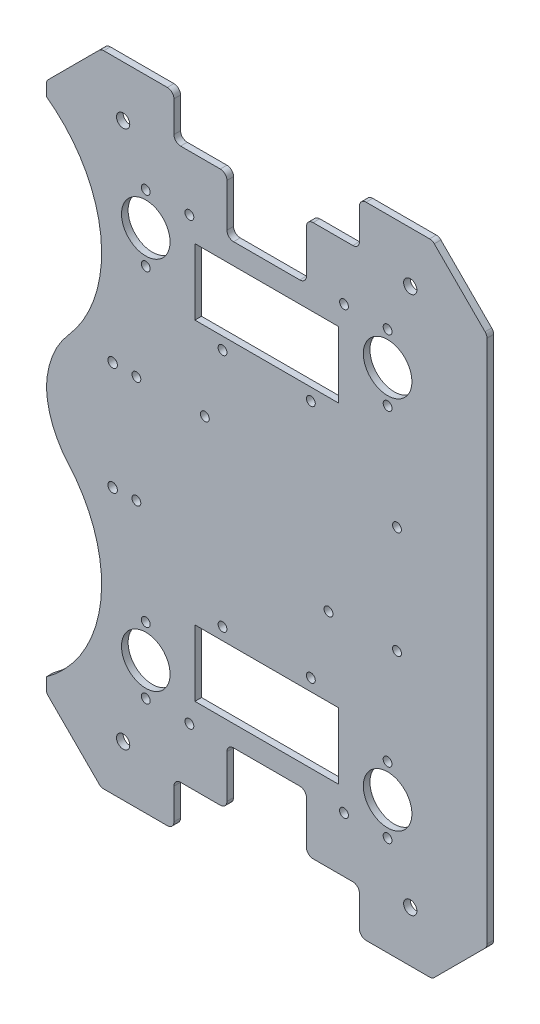
SolidWorks part; units mm, degrees
material "Alliage 1060"
ref_plane "Plan de dessus" through (0, 0, 0) normal (0, 0, 1) x (1, 0, 0)
ref_plane "Plan de droite" through (0, 0, 0) normal (0, 1, 0) x (1, 0, 0)
ref_plane "Plan de face" through (0, 0, 0) normal (1, 0, 0) x (0, 0, -1)
sketch "Esquisse1" plane through (0, 0, 0) normal (0, 0, 1) x (1, 0, 0)
  line L0 (0, 0) -> (-150, 0)
  line L1 (-150, 0) -> (-174.7487, 24.7487)
  line L2 (-174.7487, 24.7487) -> (-174.7487, 264.7487)
  line L3 (-174.7487, 264.7487) -> (-150, 289.4975)
  line L4 (-150, 289.4975) -> (0, 289.4975)
  line L5 (0, 289.4975) -> (24.7487, 264.7487)
  line L6 (24.7487, 264.7487) -> (24.7487, 24.7487)
  line L7 (24.7487, 24.7487) -> (0, 0)
  dimension "D1" = 240
  dimension "D2" = 35
  dimension "D3" = 135
  dimension "D4" = 150
extrude "Base" add sketch "Esquisse1" along normal blind 3
sketch "Esquisse3" plane through (0, 0, 0) normal (0, 0, -1) x (-1, 0, 0)
  line L0 (117, 0) -> (117, 20)
  line L1 (150, 0) -> (0, 0) construction
  line L2 (117, 20) -> (93, 20)
  line L3 (93, 20) -> (93, 45.5)
  line L4 (93, 45.5) -> (57, 45.5)
  line L5 (57, 45.5) -> (57, 20)
  line L6 (57, 20) -> (33, 20)
  line L7 (33, 20) -> (33, 0)
  line L8 (-24.7487, 144.7487) -> (174.7487, 144.7487) construction
  line L9 (-24.7487, 24.7487) -> (-24.7487, 264.7487) construction
  line L10 (174.7487, 264.7487) -> (174.7487, 24.7487) construction
  line L11 (33, 0) -> (117, 0)
  line L12 (33, 289.4975) -> (117, 289.4975)
  line L13 (117, 289.4975) -> (117, 269.4975)
  line L14 (117, 269.4975) -> (93, 269.4975)
  line L15 (93, 269.4975) -> (93, 243.9975)
  line L16 (93, 243.9975) -> (57, 243.9975)
  line L17 (57, 243.9975) -> (57, 269.4975)
  line L18 (57, 269.4975) -> (33, 269.4975)
  line L19 (33, 269.4975) -> (33, 289.4975)
  line L20 (75, 45.5) -> (75, -49954.5) construction
  line L21 (0, 289.4975) -> (150, 289.4975) construction
  line L22 (42.5, 234.4975) -> (107.5, 234.4975)
  line L23 (42.5, 234.4975) -> (42.5, 204.4975)
  line L24 (42.5, 204.4975) -> (107.5, 204.4975)
  line L25 (107.5, 234.4975) -> (107.5, 204.4975)
  line L26 (107.5, 55) -> (107.5, 85)
  line L27 (42.5, 85) -> (107.5, 85)
  line L28 (42.5, 55) -> (107.5, 55)
  line L29 (42.5, 55) -> (42.5, 85)
  circle A0 centre (40, 45) radius 2
  circle A1 centre (110, 45) radius 2
  circle A2 centre (110, 244.4975) radius 2
  circle A3 centre (40, 244.4975) radius 2
  point P4 (75, 45.5)
  point P11 (75, 0)
  point P40 (75, 234.4975)
  dimension "D7" = 4
  dimension "D5" = 25
  dimension "D1" = 20
  dimension "D2" = 24
  dimension "D3" = 36
  dimension "D4" = 25.5
  dimension "D6" = 7
  dimension "D8" = 55
  dimension "D9" = 30
  dimension "D10" = 65
extrude "Enlèv. mat.-Extru.1" cut sketch "Esquisse3" against normal through all
fillet "Congé1" radius 3 24 edges at (-174.7487, 24.7487, 1.5) (24.7487, 24.7487, 1.5) (0, 0, 1.5) (-117, 20, 1.5) (-93, 45.5, 1.5) (-93, 20, 1.5) (-150, 0, 1.5) (-117, 0, 1.5) (-57, 45.5, 1.5) (-33, 20, 1.5) (-57, 20, 1.5) (-33, 0, 1.5) (24.7487, 264.7487, 1.5) (-117, 269.4975, 1.5) (-93, 243.9975, 1.5) (-174.7487, 264.7487, 1.5) (-150, 289.4975, 1.5) (-117, 289.4975, 1.5) (-93, 269.4975, 1.5) (-57, 243.9975, 1.5) (-33, 269.4975, 1.5) (-57, 269.4975, 1.5) (-33, 289.4975, 1.5) (0, 289.4975, 1.5)
sketch "Esquisse6" plane through (0, 0, 3) normal (0, 0, 1) x (1, 0, 0)
  line L0 (-129.7487, 60) -> (-129.7487, 75) construction
  line L1 (-129.7487, 60) -> (-129.7487, 45) construction
  line L2 (-75, 231.5685) -> (-75, -49768.4315) construction
  line L4 (-42.5, 204.4975) -> (-107.5, 204.4975) construction
  line L5 (-203.2843, 144.7487) -> (49796.7157, 144.7487) construction
  line L6 (-174.7487, 263.5061) -> (-174.7487, 25.9914) construction
  line L15 (-148.7574, 0) -> (-120, 0) construction
  circle A25 centre (-129.7487, 45) radius 2
  circle A26 centre (-129.7487, 75) radius 2
  circle A27 centre (-129.7487, 60) radius 11
  circle A31 centre (-20.2513, 45) radius 2
  circle A32 centre (-20.2513, 75) radius 2
  circle A33 centre (-20.2513, 60) radius 11
  circle A34 centre (-20.2513, 229.4975) radius 11
  circle A35 centre (-20.2513, 214.4975) radius 2
  circle A36 centre (-20.2513, 244.4975) radius 2
  circle A37 centre (-129.7487, 229.4975) radius 11
  circle A38 centre (-129.7487, 214.4975) radius 2
  circle A39 centre (-129.7487, 244.4975) radius 2
  point P15 (-75, 204.4975)
  point P20 (-174.7487, 144.7487)
  dimension "D2" = 4
  dimension "D3" = 15
  dimension "D4" = 15
  dimension "D9" = 45
  dimension "D13" = 22
  dimension "D15" = 60
extrude "Perçage pour billes" cut sketch "Esquisse6" against normal up to next
sketch "Esquisse8" plane through (0, 0, 3) normal (0, 0, 1) x (1, 0, 0)
  line L0 (-75, 243.9975) -> (-75, 85) construction
  line L1 (-60, 243.9975) -> (-90, 243.9975) construction
  line L2 (-107.5, 85) -> (-42.5, 85) construction
  line L3 (-120, 289.4975) -> (-148.7574, 289.4975) construction
  line L4 (-117, 272.4975) -> (-117, 286.4975) construction
  line L5 (-148.7574, 0) -> (-120, 0) construction
  line L6 (-117, 3) -> (-117, 17) construction
  circle A0 centre (-140, 23) radius 3
  circle A1 centre (-140, 266.4975) radius 3
  circle A2 centre (-10, 266.4975) radius 3
  circle A3 centre (-10, 23) radius 3
  dimension "D1" = 23
  dimension "D2" = 23
  dimension "D3" = 6
  dimension "D4" = 23
  dimension "D5" = 23
  dimension "D6" = 6
extrude "Perçage pour profilé" cut sketch "Esquisse8" against normal up to next
sketch "Esquisse10" plane through (0, 0, 3) normal (0, 0, 1) x (1, 0, 0)
  line L0 (-174.7487, 263.5061) -> (-174.7487, 25.9914) construction
  line L1 (-75, 204.4975) -> (-75, 85) construction
  line L2 (-98.75, 169.6975) -> (-75, 169.6975) construction
  line L3 (-42.5, 204.4975) -> (-107.5, 204.4975) construction
  line L4 (-75, 169.6975) -> (21.8665, 169.6975) construction
  line L5 (-174.7487, 144.7487) -> (24.7487, 144.7487) construction
  line L6 (24.7487, 25.9914) -> (24.7487, 263.5061) construction
  line L7 (-107.5, 85) -> (-42.5, 85) construction
  line L8 (-133.75, 169.6975) -> (-98.75, 169.6975) construction
  line L9 (-107.5, 219.4975) -> (-42.5, 219.4975) construction
  line L10 (-107.5, 204.4975) -> (-107.5, 234.4975) construction
  line L11 (-42.5, 234.4975) -> (-42.5, 204.4975) construction
  line L12 (-75, 119.8) -> (-139.6239, 119.8) construction
  line L13 (-75, 119.8) -> (10.2968, 119.8) construction
  circle A8 centre (-98.75, 169.6975) radius 1.75
  circle A9 centre (-95, 198.4975) radius 1.75
  circle A10 centre (-133.75, 169.6975) radius 1.75
  circle A11 centre (-55, 198.4975) radius 1.75
  circle A18 centre (-55, 91) radius 1.75
  circle A19 centre (-95, 91) radius 1.75
  circle A20 centre (-46.75, 169.6975) radius 1.75
  circle A21 centre (-15.75, 169.6975) radius 1.75
  circle A22 centre (-103.25, 119.8) radius 1.75
  circle A23 centre (-134.25, 119.8) radius 1.75
  circle A24 centre (-51.25, 119.8) radius 1.75
  circle A25 centre (-16.25, 119.8) radius 1.75
  dimension "D1" = 3.5
  dimension "D2" = 23.75
  dimension "D3" = 20
  dimension "D4" = 3.5
  dimension "D5" = 3.5
  dimension "D6" = 35
  dimension "D7" = 21
  dimension "D8" = 28.8
  dimension "D9" = 3.5
  dimension "D10" = 3.5
  dimension "D12" = 31
  dimension "D13" = 28.8
  dimension "D14" = 3.5
  dimension "D15" = 3.5
  dimension "D16" = 3.5
  dimension "D17" = 3.5
  dimension "D18" = 28.25
  dimension "D19" = 31
  dimension "D21" = 35
  dimension "D11" = 28.25
  dimension "D20" = 23.75
sketch "Esquisse11" plane through (0, 0, 3) normal (0, 0, 1) x (1, 0, 0)
  line L0 (-174.7487, 144.7487) -> (-144.7487, 144.7487) construction
  line L1 (-174.7487, 263.5061) -> (-174.7487, 25.9914) construction
  line L2 (-144.7487, 169.2487) -> (-144.7487, 120.2487) construction
  circle A0 centre (-144.7487, 169.2487) radius 2.15
  circle A1 centre (-144.7487, 120.2487) radius 2.15
  point P7 (-144.7487, 144.7487)
  point P9 (-174.7487, 144.7487)
  dimension "D3" = 4.3
  dimension "D4" = 4.3
  dimension "D1" = 49
  dimension "D2" = 30
extrude "Enlèv. mat.-Extru.4" cut sketch "Esquisse11" against normal through all
sketch "Esquisse12" plane through (0, 0, 3) normal (0, 0, 1) x (1, 0, 0)
  line L0 (-209.7487, 209.7487) -> (-209.7487, 79.7487) construction
  line L1 (-174.7487, 263.5061) -> (-174.7487, 25.9914) construction
  line L2 (-149.7487, 209.7487) -> (-149.7487, 79.7487)
  circle A2 centre (-209.7487, 209.7487) radius 60
  circle A3 centre (-209.7487, 79.7487) radius 60
  point P4 (-174.7487, 144.7487)
  point P5 (-209.7487, 144.7487)
  dimension "D1" = 130
  dimension "D2" = 120
  dimension "D3" = 120
  dimension "D4" = 35
extrude "Enlèv. mat.-Extru.5" cut sketch "Esquisse12" against normal up to next contours A2 | A3 | A3 | A2 region at (-209.7487, 79.7487, 3) region at (-209.7487, 209.7487, 3)
fillet "Congé2" radius 40 2 edges at (-174.7487, 128.4827, 1.5) (-174.7487, 161.0148, 1.5)
sketch "Esquisse13" plane through (0, 0, 0) normal (0, 0, -1) x (-1, 0, 0)
  line L0 (95, 198.9975) -> (107.5, 198.9975) construction
  line L1 (75, 204.4975) -> (75, 85) construction
  line L2 (42.5, 204.4975) -> (107.5, 204.4975) construction
  line L3 (107.5, 85) -> (42.5, 85) construction
  line L4 (174.7487, 144.7487) -> (-24.7487, 144.7487) construction
  line L5 (-24.7487, 25.9914) -> (-24.7487, 263.5061) construction
  line L6 (107.5, 204.4975) -> (107.5, 198.9975) construction
  line L7 (103, 168.9975) -> (134, 168.9975) construction
  circle A1 centre (95, 198.9975) radius 2
  circle A2 centre (134, 168.9975) radius 2
  circle A3 centre (103, 168.9975) radius 2
  circle A5 centre (55, 198.9975) radius 2
  circle A6 centre (16, 168.9975) radius 2
  circle A7 centre (47, 120.5) radius 2
  circle A8 centre (55, 90.5) radius 2
  circle A9 centre (95, 90.5) radius 2
  circle A10 centre (16, 120.5) radius 2
  circle A11 centre (134, 120.5) radius 2
  point P22 (75, 144.7487)
  point P37 (75, 144.7487)
  dimension "D4" = 4
  dimension "D5" = 4
  dimension "D6" = 4
  dimension "D2" = 12.5
  dimension "D3" = 5.5
  dimension "D7" = 24.2487
  dimension "D8" = 28
  dimension "D9" = 31
  dimension "D1" = 2
extrude "Perçage bloc moteur" cut sketch "Esquisse13" against normal up to next
sketch "Esquisse14" plane through (0, 289.4975, 0) normal (0, 1, 0) x (1, 0, 0)
  line L0 (-75, -3) -> (-75, 0) construction
  line L1 (-60, -3) -> (-90, -3) construction
  line L2 (-60, 0) -> (-90, 0) construction
